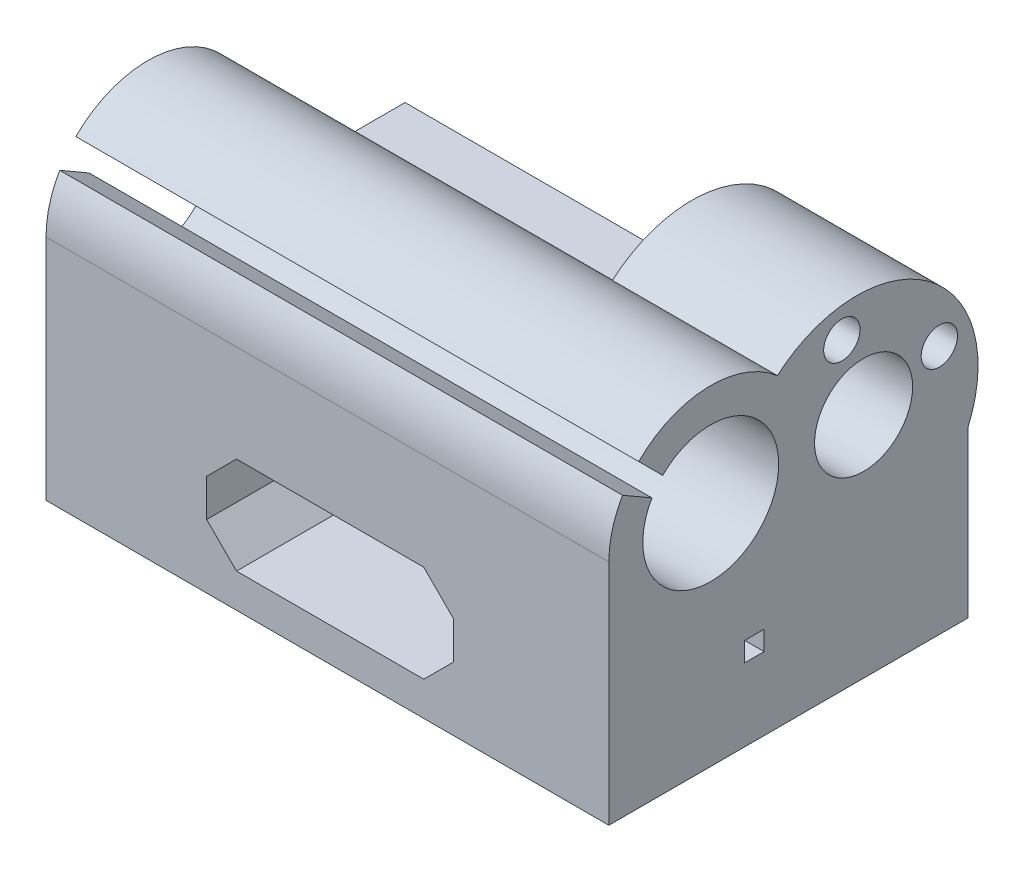
SolidWorks part; units mm, degrees
ref_plane "Front Plane" through (0, 0, 0) normal (0, 0, 1) x (1, 0, 0)
ref_plane "Top Plane" through (0, 0, 0) normal (0, 1, 0) x (1, 0, 0)
ref_plane "Right Plane" through (0, 0, 0) normal (1, 0, 0) x (0, 0, -1)
sketch "Sketch2" plane through (0, 0, 0) normal (0, 1, 0) x (1, 0, 0)
  line L1 (-29, -18.5) -> (29, -18.5)
  line L2 (-29, -18.5) -> (-29, 18.5)
  line L3 (-29, 18.5) -> (29, 18.5)
  line L4 (29, -18.5) -> (29, 18.5)
  line L5 (-29, -18.5) -> (29, 18.5) construction
  line L6 (-29, 18.5) -> (29, -18.5) construction
  point P0 (0, 0)
  dimension "D1" = 58
  dimension "D2" = 37
extrude "Boss-Extrude1" add sketch "Sketch2" along normal blind 17
sketch "Sketch3" plane through (29, 0, 0) normal (1, 0, 0) x (0, 0, -1)
  line L0 (-18.5, 0) -> (18.5, 0) construction
  line L1 (-18.5, 23.5) -> (-18.5, 17)
  line L2 (-18.5, 17) -> (-18.5, 0) construction
  line L5 (2.5, 23.5) -> (2.5, 17)
  line L6 (-18.5, 17) -> (18.5, 17) construction
  line L7 (-18.5, 17) -> (2.5, 17)
  arc A0 (2.5, 23.5) -> (-18.5, 23.5) centre (-8, 23.5) ccw
  dimension "D2" = 21
  dimension "D4" = 23.5
  dimension "D5" = 10.5
extrude "Boss-Extrude2" add sketch "Sketch3" against normal up to surface (58 mm away) up to face at (-29, 8.5, 0)
sketch "Sketch4" plane through (29, 0, 0) normal (1, 0, 0) x (0, 0, -1)
  line L1 (-18.5, 0) -> (18.5, 0) construction
  circle A0 centre (7.0436, 22) radius 12.5
  dimension "D1" = 25
  dimension "D2" = 22
extrude "Boss-Extrude3" add sketch "Sketch4" against normal blind 17
sketch "Sketch5" plane through (0, 0, -18.5) normal (0, 0, -1) x (-1, 0, 0)
  line L0 (-13, 6.57) -> (-13, 10.427)
  line L1 (-13, 10.427) -> (-9.93, 13.497)
  line L2 (-9.93, 13.497) -> (9.37, 13.497)
  line L3 (9.37, 13.497) -> (12.44, 10.427)
  line L4 (12.44, 10.427) -> (12.44, 6.57)
  line L5 (12.44, 6.57) -> (9.37, 3.5)
  line L6 (9.37, 3.5) -> (-9.93, 3.5)
  line L7 (-9.93, 3.5) -> (-13, 6.57)
  line L8 (-29, 0) -> (29, 0) construction
  line L9 (-29, 17) -> (-29, 0) construction
  dimension "D1" = 3.857
  dimension "D2" = 3.857
  dimension "D3" = 135
  dimension "D4" = 135
  dimension "D5" = 3.07
  dimension "D6" = 3.07
  dimension "D7" = 3.07
  dimension "D8" = 3.07
  dimension "D9" = 19.3
  dimension "D10" = 3.5
  dimension "D11" = 16
extrude "Cut-Extrude1" cut sketch "Sketch5" against normal through all
sketch "Sketch6" plane through (0, 0, -18.5) normal (0, 0, -1) x (-1, 0, 0)
  line L0 (-29, 0) -> (29, 0) construction
  line L1 (-29, 17) -> (-29, 0) construction
  circle A0 centre (-23, 8.5) radius 4.076
  circle A1 centre (22, 8.5) radius 4.076
  dimension "D5" = 8.152
  dimension "D6" = 8.152
  dimension "D1" = 8.5
  dimension "D2" = 8.5
  dimension "D3" = 6
  dimension "D4" = 51
extrude "Cut-Extrude2" cut sketch "Sketch6" against normal blind 23
sketch "Sketch7" plane through (29, 0, 0) normal (1, 0, 0) x (0, 0, -1)
  line L0 (-18.5, 23.5) -> (-18.5, 0) construction
  line L1 (-18.5, 0) -> (18.5, 0) construction
  circle A0 centre (-8, 23.5) radius 7
  circle A1 centre (7.7501, 23.5) radius 5.05
  dimension "D1" = 10.1
  dimension "D2" = 14
  dimension "D3" = 26.2501
  dimension "D4" = 23.5
extrude "Cut-Extrude3" cut sketch "Sketch7" against normal through all
sketch "Sketch8" plane through (29, 0, 0) normal (1, 0, 0) x (0, 0, -1)
  line L0 (7.7501, 23.5) -> (5.5097, 31.31) construction
  line L3 (7.7501, 23.5) -> (15.5601, 25.7405) construction
  line L4 (5.5097, 31.31) -> (6.0267, 29.5077) construction
  line L7 (15.5601, 25.7405) -> (13.7578, 25.2235) construction
  circle A1 centre (5.5097, 31.31) radius 1.875
  circle A2 centre (15.5601, 25.7405) radius 1.875
  dimension "D1" = 3.75
  dimension "D2" = 6.25
  dimension "D3" = 3.75
  dimension "D7" = 6.25
extrude "Cut-Extrude4" cut sketch "Sketch8" against normal through all
sketch "Sketch9" plane through (12, 0, 0) normal (-1, 0, 0) x (0, 0, 1)
  circle A0 centre (-5.5097, 31.31) radius 2.75
  circle A1 centre (-15.5601, 25.7405) radius 2.75
  dimension "D1" = 5.5
  dimension "D2" = 5.5
sketch "Sketch10" plane through (29, 0, 0) normal (1, 0, 0) x (0, 0, -1)
  line L0 (-8, 23.5) -> (-15.4246, 30.9246) construction
  line L1 (-8, 23.5) -> (-29.5432, 23.5) construction
  line L2 (-8, 23.5) -> (-17.0933, 28.75) construction
  line L3 (-12.9497, 28.4497) -> (-15.4246, 30.9246)
  line L4 (-17.0933, 28.75) -> (-14.0622, 27)
  arc A0 (-1.1397, 31.449) -> (-18.5, 23.5) centre (-8, 23.5) ccw construction
  arc A1 (-12.9497, 28.4497) -> (-14.0622, 27) centre (-8, 23.5) ccw
  arc A2 (-18.5, 23.5) -> (-17.0933, 28.75) centre (-8, 23.5) ccw
  circle A3 centre (-8, 23.5) radius 7 construction
  circle M9 centre (-8, 23.5) radius 7
  arc M13 (-1.1397, 31.449) -> (-18.5, 23.5) centre (-8, 23.5) ccw
  dimension "D1" = 15
  dimension "D2" = 30
extrude "Cut-Extrude5" cut sketch "Sketch10" against normal through all contours L4 L3 M13 M9 region at (29, 28.8823, 15.0143)
sketch "Sketch12" plane through (-29, 0, 0) normal (-1, 0, 0) x (0, 0, 1)
  line L0 (-18.5, 17) -> (-18.5, 0) construction
  line L1 (4.5, 7.5) -> (2.5, 7.5)
  line L2 (4.5, 7.5) -> (4.5, 9.5)
  line L3 (4.5, 9.5) -> (2.5, 9.5)
  line L4 (2.5, 7.5) -> (2.5, 9.5)
  line L5 (-18.5, 0) -> (18.5, 0) construction
  dimension "D1" = 23
  dimension "D2" = 2
  dimension "D3" = 2
  dimension "D4" = 7.5
extrude "Cut-Extrude6" cut sketch "Sketch12" against normal blind 8
mirror "Mirror1" about plane through (0, 0, 0) normal (1, 0, 0) of "Cut-Extrude6"
